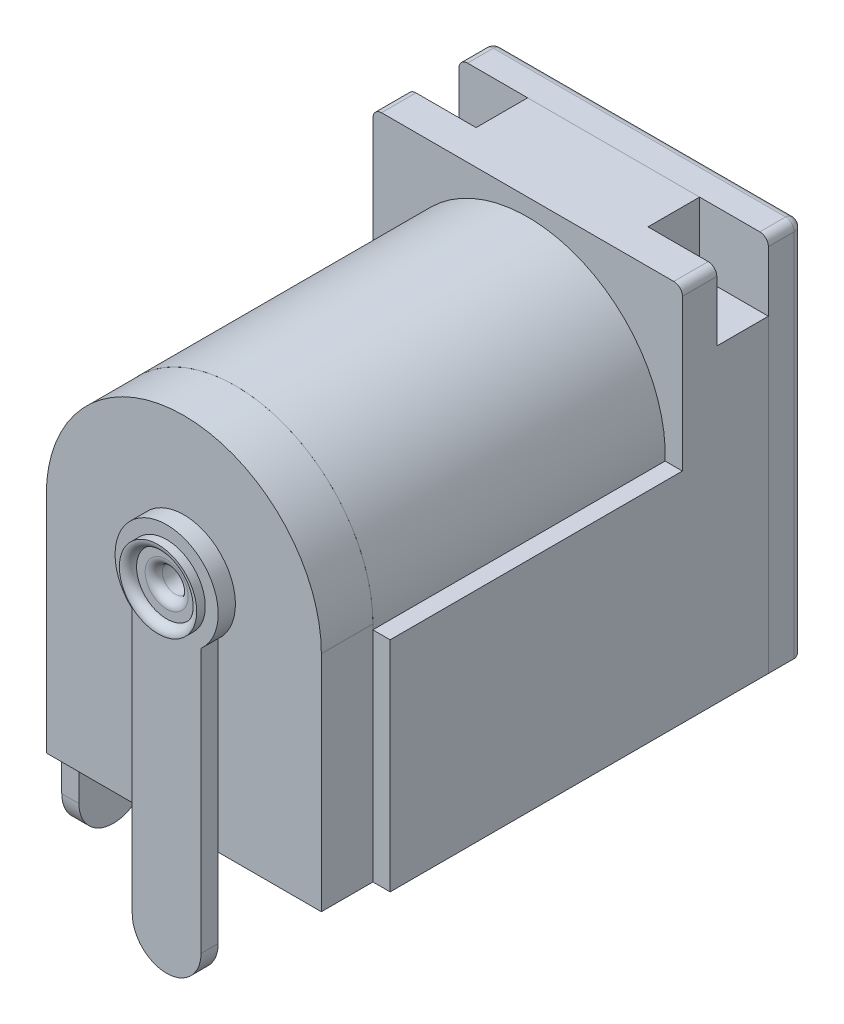
SolidWorks part; units mm, degrees
ref_plane "Front Plane" through (0, 0, 0) normal (0, 0, 1) x (1, 0, 0)
ref_plane "Top Plane" through (0, 0, 0) normal (0, 1, 0) x (1, 0, 0)
ref_plane "Right Plane" through (0, 0, 0) normal (1, 0, 0) x (0, 0, -1)
sketch "Sketch1" plane through (0, 0, 0) normal (0, 0, 1) x (1, 0, 0)
  line L1 (4.5, -3.175) -> (-4.5, -3.175)
  line L2 (4.5, -3.175) -> (4.5, 3.175)
  line L3 (4.5, 3.175) -> (-4.5, 3.175)
  line L4 (-4.5, -3.175) -> (-4.5, 3.175)
  line L5 (4.5, -3.175) -> (-4.5, 3.175) construction
  line L6 (4.5, 3.175) -> (-4.5, -3.175) construction
  point P0 (0, 0)
  dimension "D1" = 6.35
  dimension "D2" = 9
extrude "Boss-Extrude1" add sketch "Sketch1" along normal blind 12
sketch "Sketch2" plane through (0, 0, 0) normal (0, 0, -1) x (-1, 0, 0)
  line L1 (4.5, 7.825) -> (-4.5, 7.825)
  line L2 (4.5, 7.825) -> (4.5, -3.175)
  line L3 (4.5, -3.175) -> (-4.5, -3.175)
  line L4 (-4.5, 7.825) -> (-4.5, -3.175)
  line L5 (4.5, 7.825) -> (-4.5, -3.175) construction
  line L6 (4.5, -3.175) -> (-4.5, 7.825) construction
  point P0 (0, 2.325)
  dimension "D1" = 11
extrude "Boss-Extrude2" add sketch "Sketch2" against normal blind 3.5
sketch "Sketch4" plane through (0, 0, 0) normal (0, 0, -1) x (-1, 0, 0)
  line L1 (4.5, 7.825) -> (-4.5, 7.825) construction
  circle A0 centre (0, 3.325) radius 4
  point P6 (0, 7.325)
  dimension "D1" = 8
  dimension "D2" = 0.5
extrude "Boss-Extrude3" add sketch "Sketch4" against normal up to surface (12 mm away) up to face at (0, 0, 12)
ref_plane "Plane1" through (0, 0, 1.75) normal (0, 0, 1) x (1, 0, 0)
sketch "Sketch5" plane through (0, 0, 1.75) normal (0, 0, 1) x (1, 0, 0)
  line L0 (0, 0) -> (0, 7.825) construction
  line L1 (-2.5, 5.825) -> (-4.5, 5.825)
  line L2 (-2.5, 5.825) -> (-2.5, 7.825)
  line L3 (-2.5, 7.825) -> (-4.5, 7.825)
  line L4 (-4.5, 5.825) -> (-4.5, 7.825)
  line L5 (-2.5, 5.825) -> (-4.5, 7.825) construction
  line L6 (-2.5, 7.825) -> (-4.5, 5.825) construction
  line L7 (-4.5, 7.825) -> (4.5, 7.825) construction
  line L8 (2.5, 7.825) -> (4.5, 5.825) construction
  line L9 (2.5, 5.825) -> (4.5, 7.825) construction
  line L10 (4.5, 5.825) -> (4.5, 7.825)
  line L11 (2.5, 7.825) -> (4.5, 7.825)
  line L12 (2.5, 5.825) -> (2.5, 7.825)
  line L13 (2.5, 5.825) -> (4.5, 5.825)
  point P0 (-3.5, 6.825)
  point P16 (3.5, 6.825)
  dimension "D1" = 2
extrude "Cut-Extrude1" cut sketch "Sketch5" against normal mid plane 1.5
fillet "Fillet1" radius 0.25 8 edges at (0, -3.175, 0) (4.5, 2.325, 0) (0, 7.825, 0) (-4.5, 2.325, 0) (-4.5, 7.825, 0.5) (-4.5, 7.825, 3) (4.5, 7.825, 0.5) (4.5, 7.825, 3)
sketch "Sketch6" plane through (0, 0, 0) normal (0, 0, -1) x (-1, 0, 0)
  circle A0 centre (0, 3.325) radius 3.25
  dimension "D1" = 6.5
extrude "Cut-Extrude2" cut sketch "Sketch6" against normal up to next
sketch "Sketch7" plane through (0, 0, 12) normal (0, 0, 1) x (1, 0, 0)
  line L0 (-4.5, -3.175) -> (4.5, -3.175) construction
  line L1 (4, 1.325) -> (-4, 1.325)
  line L2 (4, 1.325) -> (4, -2.675)
  line L3 (4, -2.675) -> (-4, -2.675)
  line L4 (-4, 1.325) -> (-4, -2.675)
  line L5 (4, 1.325) -> (-4, -2.675) construction
  line L6 (4, -2.675) -> (-4, 1.325) construction
  line L7 (-4.5, 3.175) -> (-4.5, -3.175) construction
  point P0 (0, -0.675)
  dimension "D1" = 0.5
  dimension "D2" = 0.5
  dimension "D3" = 4
extrude "Cut-Extrude3" cut sketch "Sketch7" against normal up to surface (11 mm away) up to face at (3.6604, 6.9854, 1)
sketch "Sketch8" plane through (0, 0, 12) normal (0, 0, 1) x (1, 0, 0)
  line L0 (-4, 3.325) -> (-4, -3.175)
  line L1 (4, 3.325) -> (4, -3.175)
  line L2 (-4, -3.175) -> (4, -3.175)
  line L3 (-4.5, -3.175) -> (4.5, -3.175) construction
  arc A0 (-4, 3.325) -> (4, 3.325) centre (0, 3.325) cw
  arc A1 (3.9972, 3.175) -> (-3.9972, 3.175) centre (0, 3.325) ccw construction
extrude "Boss-Extrude5" add sketch "Sketch8" along normal blind 1.5 separate body
sketch "Sketch9" plane through (0, 7.825, 0) normal (0, 1, 0) x (1, 0, 0)
  line L0 (-5, -1) -> (5, -1)
  line L1 (4.25, -1) -> (4.5, -1) construction
  line L2 (0, -1) -> (0, 0) construction
  dimension "D1" = 10
split "Split1" trim tools "Sketch9" bodies to split 106 resulting bodies 111 112
sketch "Sketch10" plane through (0, 0, 13.5) normal (0, 0, 1) x (1, 0, 0)
  circle A0 centre (0, 3.325) radius 1.5
  dimension "D1" = 3
extrude "Cut-Extrude4" cut sketch "Sketch10" against normal through all
sketch "Sketch11" plane through (0, 0, 12) normal (0, 0, -1) x (-1, 0, 0)
  circle A0 centre (0, 3.325) radius 1.5
  dimension "D1" = 3
extrude "Boss-Extrude6" add sketch "Sketch11" against normal blind 2 separate body
sketch "Sketch12" plane through (0, 0, 12) normal (0, 0, -1) x (-1, 0, 0)
  circle A0 centre (0, 3.325) radius 1
  dimension "D1" = 2
extrude "Boss-Extrude7" add sketch "Sketch12" along normal offset from surface (11 mm away) 1 up to face at (-3.25, 3.325, 0)
fillet "Fillet2" radius 0.7 1 edges at (1, 3.325, 1) type face fillet first side face at (1, 3.325, 1) second side face at (1, 3.325, 1)
sketch "Sketch13" plane through (0, 0, 13.5) normal (0, 0, 1) x (1, 0, 0)
  line L0 (-1, 2.207) -> (-1, -5.475)
  line L4 (1, -5.475) -> (1, 2.207)
  line L5 (0, 3.325) -> (0, -6.475) construction
  line L6 (-4, -3.175) -> (4, -3.175) construction
  circle A0 centre (0, 3.325) radius 1.5 construction
  circle A1 centre (0, 3.325) radius 1.5 construction
  arc A2 (1, 2.207) -> (-1, 2.207) centre (0, 3.325) cw
  arc A3 (-1, -5.475) -> (1, -5.475) centre (0, -5.475) ccw
  dimension "D1" = 2
  dimension "D2" = 3.3
extrude "Boss-Extrude8" add sketch "Sketch13" along normal up to surface (0.5 mm away) up to face at (-1.5, 3.325, 14)
sketch "Sketch14" plane through (0, 0, 12) normal (0, 0, 1) x (1, 0, 0)
  line L0 (-4.5, 3.175) -> (-4.5, -3.175) construction
  line L1 (-4, 0.675) -> (-4.5, 0.675)
  line L2 (-4, 0.675) -> (-4, 1.175)
  line L3 (-4, 1.175) -> (-4.5, 1.175)
  line L4 (-4.5, 0.675) -> (-4.5, 1.175)
  line L5 (-4, 0.675) -> (-4.5, 1.175) construction
  line L6 (-4, 1.175) -> (-4.5, 0.675) construction
  line L7 (-4, 1.325) -> (-4, -2.675) construction
  line L8 (-3.9972, 3.175) -> (-4.5, 3.175) construction
  point P0 (-4.25, 0.925)
  dimension "D1" = 0.5
  dimension "D2" = 2
extrude "Cut-Extrude5" cut sketch "Sketch14" against normal blind 2
sketch "Sketch15" plane through (0, 0, 12) normal (0, 0, 1) x (1, 0, 0)
  line L0 (-3.5, 0.675) -> (-4.5, 0.675)
  line L1 (-4.5, 0.675) -> (-4.5, -3.175) construction
  line L2 (-4.55, 0.625) -> (-4.55, -3.175)
  line L3 (-4.5, -3.175) -> (4.5, -3.175) construction
  line L4 (-4.5, 0.675) -> (-4, 0.675) construction
  arc A0 (-4.5, 0.675) -> (-4.55, 0.625) centre (-4.5, 0.625) ccw
  dimension "D1" = 0.05
  dimension "D2" = 1
extrude "Extrude-Thin1" add sketch "Sketch15" against normal up to surface (2 mm away) separate body thin up to face at (-4.25, 0.925, 10) thin type one direction wall 0.5
sketch "Sketch16" plane through (-5.05, 0, 0) normal (-1, 0, 0) x (0, 0, 1)
  line L0 (10, -3.175) -> (10, -5.475)
  line L1 (12, -5.475) -> (12, -3.175)
  line L2 (10, -3.175) -> (12, -3.175)
  line L3 (13.5, -6.475) -> (11, -6.475) construction
  line L4 (13.5, -6.475) -> (14, -6.475) construction
  line L5 (13.5, -5.475) -> (13.5, -6.475) construction
  arc A0 (10, -5.475) -> (12, -5.475) centre (11, -5.475) ccw
  point P5 (11, -6.475)
extrude "Boss-Extrude9" add sketch "Sketch16" against normal up to surface (0.5 mm away) up to face at (-4.55, -1.275, 11)
ref_plane "Plane2" through (0, 0, 7.5) normal (0, 0, 1) x (1, 0, 0)
sketch "Sketch17" plane through (0, 0, 7.5) normal (0, 0, 1) x (1, 0, 0)
  line L0 (-1, -3.175) -> (-1, -5.475)
  line L1 (1, -5.475) -> (1, -3.175)
  line L2 (-4.5, -3.175) -> (4.5, -3.175) construction
  line L3 (1, -3.175) -> (-1, -3.175) construction
  line L4 (0, -5.475) -> (0, 0) construction
  line L5 (1, -3.175) -> (1, -1.675)
  line L6 (1, -1.675) -> (-1, -1.675)
  line L7 (-1, -1.675) -> (-1, -3.175)
  arc A0 (-1, -5.475) -> (1, -5.475) centre (0, -5.475) ccw
  arc A1 (-1, -5.475) -> (1, -5.475) centre (0, -5.475) ccw construction
  arc A2 (-1, -5.475) -> (1, -5.475) centre (0, -5.475) ccw construction
  dimension "D1" = 2
  dimension "D2" = 1.5
extrude "Boss-Extrude10" add sketch "Sketch17" against normal blind 0.5 separate body
sketch "Sketch18" plane through (0, 0, 0) normal (1, 0, 0) x (0, 0, -1)
  line L0 (-1, -2.675) -> (-1, -1.175)
  line L1 (-1.987, 0.2345) -> (-5.7457, 1.6026)
  line L2 (0, 7.575) -> (0, -2.925) construction
  line L4 (-1, -2.675) -> (-12, -2.675) construction
  line L5 (-6.2588, 0.1931) -> (-7.223, 1.3421) construction
  line L6 (-6.2588, 0.1931) -> (-5.7457, 1.6026) construction
  arc A0 (-1, -1.175) -> (-1.987, 0.2345) centre (-2.5, -1.175) ccw
  arc A1 (-5.7457, 1.6026) -> (-7.223, 1.3421) centre (-6.2588, 0.1931) ccw
  dimension "D3" = 1.5
  dimension "D6" = 1.5
  dimension "D1" = 1
  dimension "D2" = 1.5
  dimension "D4" = 70
  dimension "D5" = 4
  dimension "D7" = 60
extrude "Extrude-Thin2" add sketch "Sketch18" along normal mid plane 4 separate body thin thin type one direction reverse wall 0.5
sketch "Sketch21" plane through (0, 0, 14) normal (0, 0, 1) x (1, 0, 0)
  circle A0 centre (0, 3.325) radius 0.875
  circle A1 centre (0, 3.325) radius 1.5 construction
  circle A2 centre (0, 3.325) radius 1.5 construction
  dimension "D1" = 1.75
extrude "Extrude-Thin3" add sketch "Sketch21" along normal blind 0.25 thin thin type one direction wall 0.25
sketch "Sketch22" plane through (0, 0, 14) normal (0, 0, 1) x (1, 0, 0)
  circle A0 centre (0, 3.325) radius 0.375
  dimension "D1" = 0.75
extrude "Cut-Extrude6" cut sketch "Sketch22" against normal blind 3
fillet "Fillet3" radius 0.25 2 edges at (0.375, 3.325, 14) (0.875, 3.325, 14.25)
